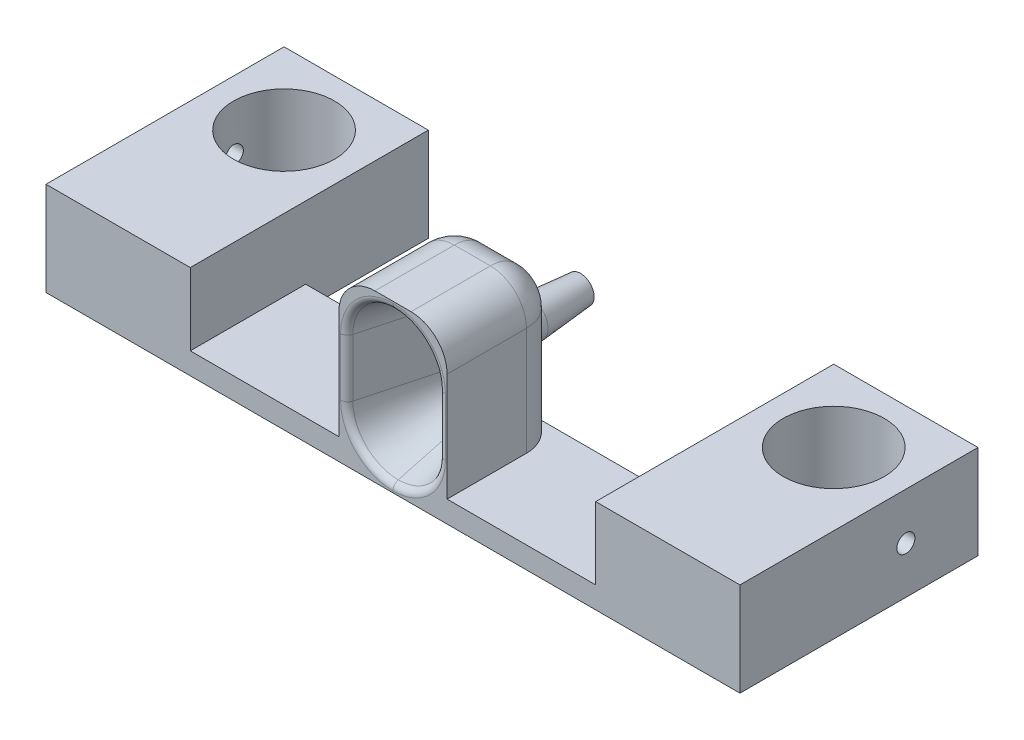
SolidWorks part; units mm, degrees
ref_plane "Front Plane" through (0, 0, 0) normal (0, 0, 1) x (1, 0, 0)
ref_plane "Top Plane" through (0, 0, 0) normal (0, 1, 0) x (1, 0, 0)
ref_plane "Right Plane" through (0, 0, 0) normal (1, 0, 0) x (0, 0, -1)
sketch "Sketch1" plane through (0, 0, 0) normal (0, 1, 0) x (1, 0, 0)
  line L0 (31.1, 0) -> (28.1, 0) construction
  line L1 (38.1, 7) -> (38.1, 10) construction
  line L2 (-38.1, 7) -> (-38.1, 10) construction
  line L3 (-45.1, 0) -> (-48.1, 0) construction
  line L4 (-31.1, 0) -> (-28.1, 0) construction
  line L5 (45.1, 0) -> (48.1, 0) construction
  line L6 (-38.1, -7) -> (-38.1, -23) construction
  line L11 (38.1, -7) -> (38.1, -23) construction
  line L12 (-28.1, -7) -> (-28.1, 10)
  line L13 (-48.1, 10) -> (-28.1, 10)
  line L14 (-48.1, 10) -> (-48.1, -23)
  line L15 (-48.1, -23) -> (-28.1, -23)
  line L17 (28.1, 10) -> (48.1, 10)
  line L19 (28.1, -23) -> (48.1, -23)
  line L20 (48.1, 10) -> (48.1, -23)
  line L21 (-28.1, -7) -> (28.1, -7)
  line L23 (-28.1, -23) -> (28.1, -23)
  line L25 (28.1, 10) -> (28.1, -7)
  circle A0 centre (-38.1, 0) radius 7
  circle A1 centre (38.1, 0) radius 7
extrude "Boss-Extrude1" add sketch "Sketch1" along normal blind 13
sketch "Sketch2" plane through (0, 13, 0) normal (0, 1, 0) x (1, 0, 0)
  line L0 (-48.1, -23) -> (48.1, -23) construction
  line L1 (-28.1, -7) -> (28.1, -7)
  line L2 (-28.1, -7) -> (-28.1, -23)
  line L3 (-28.1, -23) -> (28.1, -23)
  line L4 (28.1, -7) -> (28.1, -23)
extrude "Cut-Extrude1" cut sketch "Sketch2" against normal blind 10
sketch "Sketch3" plane through (0, 3, 0) normal (0, 1, 0) x (1, 0, 0)
  line L0 (0, -7) -> (7.5, -7) construction
  line L1 (28.1, -7) -> (-28.1, -7) construction
  line L2 (0, -7) -> (-7.5, -7) construction
  line L3 (-28.1, -23) -> (28.1, -23) construction
  line L4 (-7.5, -7) -> (7.5, -7)
  line L5 (-7.5, -7) -> (-7.5, -23)
  line L6 (-7.5, -23) -> (7.5, -23)
  line L7 (7.5, -7) -> (7.5, -23)
extrude "Cut-Extrude2" cut sketch "Sketch3" against normal up to next
sketch "Sketch4" plane through (0, 0, 23) normal (0, 0, 1) x (1, 0, 0)
  line L0 (7.5, 0) -> (7.5, 3) construction
  line L1 (-7.5, 0) -> (7.5, 0)
  line L2 (-7.5, 0) -> (-7.5, 23)
  line L3 (-7.5, 23) -> (7.5, 23)
  line L4 (7.5, 0) -> (7.5, 23)
extrude "Boss-Extrude2" add sketch "Sketch4" against normal blind 16
sketch "Sketch5" plane through (0, 0, 23) normal (0, 0, 1) x (1, 0, 0)
  line L0 (0, 23) -> (0, 22) construction
  line L1 (7.5, 23) -> (-7.5, 23) construction
  line L2 (0, 0) -> (0, 1) construction
  line L3 (-7.5, 13) -> (-6.5, 13) construction
  line L4 (-7.5, 23) -> (-7.5, 3) construction
  line L5 (7.5, 13) -> (6.5, 13) construction
  line L6 (7.5, 3) -> (7.5, 23) construction
  line L12 (-6.5, 22) -> (6.5, 22)
  line L13 (-6.5, 22) -> (-6.5, 1)
  line L14 (-6.5, 1) -> (6.5, 1)
  line L15 (6.5, 22) -> (6.5, 1)
extrude "Cut-Extrude3" cut sketch "Sketch5" against normal blind 12
sketch "Sketch6" plane through (0, 0, 11) normal (0, 0, 1) x (1, 0, 0)
  line L0 (0, 11.4642) -> (0, 6.9642) construction
  circle A0 centre (0, 11.4642) radius 1.5
  circle A1 centre (0, 6.9642) radius 1.05
extrude "Cut-Extrude4" cut sketch "Sketch6" against normal up to next
sketch "Sketch7" plane through (0, 0, 7) normal (0, 0, -1) x (-1, 0, 0)
  circle A0 centre (0, 11.4642) radius 2.5
  circle A2 centre (0, 11.4642) radius 1.5
extrude "Boss-Extrude3" add sketch "Sketch7" along normal blind 10
chamfer "Chamfer1" distance 7 angle 5 1 edges at (-2.5, 11.4642, -3) first distance on face at (-2.5, 11.4642, -3)
sketch "Sketch8" plane through (-48.1, 0, 0) normal (-1, 0, 0) x (0, 0, 1)
  circle A0 centre (0, 6.5) radius 1.25
extrude "Cut-Extrude5" cut sketch "Sketch8" against normal up to next
sketch "Sketch9" plane through (48.1, 0, 0) normal (1, 0, 0) x (0, 0, -1)
  circle A0 centre (0, 6.5) radius 1.25
extrude "Cut-Extrude6" cut sketch "Sketch9" against normal up to next
fillet "Fillet7" radius 6.5 4 edges at (-6.5, 1, 17) (6.5, 1, 17) (6.5, 22, 17) (-6.5, 22, 17)
chamfer "Chamfer3" distance 12 angle 15 6 edges at (-6.5, 11.5, 11) (-4.5962, 2.9038, 11) (-4.5962, 20.0962, 11) (4.5962, 2.9038, 11) (4.5962, 20.0962, 11) (6.5, 11.5, 11) first distance on face at (-6.5, 11.5, 17) first distance on face at (-3.9231, 3.5769, 17) first distance on face at (-3.9231, 19.4231, 17) first distance on face at (3.9231, 3.5769, 17) first distance on face at (3.9231, 19.4231, 17) first distance on face at (6.5, 11.5, 17)
fillet "Fillet9" radius 2 6 edges at (2.3226, 5.1774, 11) (-2.3226, 5.1774, 11) (-3.2846, 11.5, 11) (-2.3226, 17.8226, 11) (2.3226, 17.8226, 11) (3.2846, 11.5, 11)
fillet "Fillet10" radius 5 5 edges at (-7.5, 23, 15) (-7.5, 13, 7) (7.5, 23, 15) (7.5, 13, 7) (0, 23, 7)
fillet "Fillet11" radius 1 6 edges at (-4.5962, 20.0962, 23) (4.5962, 20.0962, 23) (6.5, 11.5, 23) (4.5962, 2.9038, 23) (-4.5962, 2.9038, 23) (-6.5, 11.5, 23)
fillet "Fillet15" radius 2 1 edges at (1.5, 11.4642, 11)
